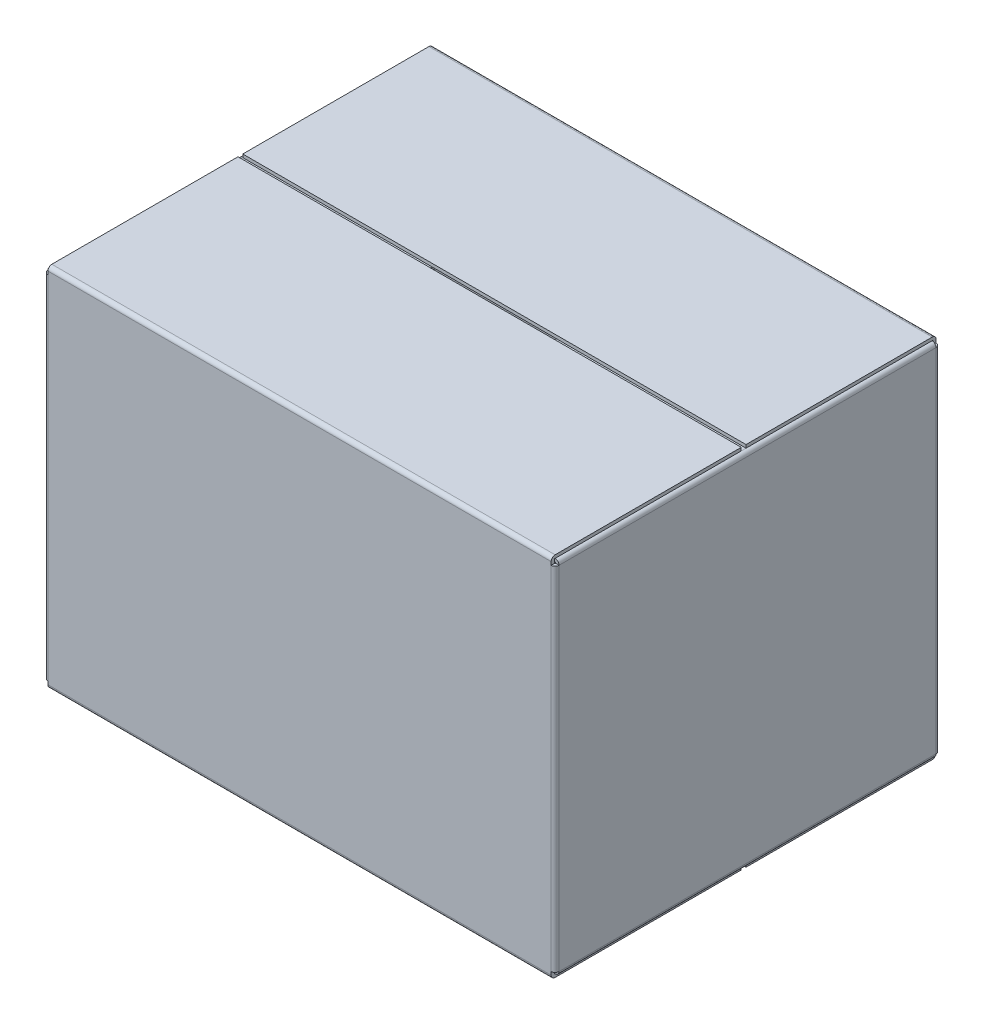
SolidWorks part; units mm, degrees
ref_plane "FRONT" through (0, 0, 0) normal (0, 0, 1) x (1, 0, 0)
ref_plane "TOP" through (0, 0, 0) normal (0, 1, 0) x (1, 0, 0)
ref_plane "RIGHT" through (0, 0, 0) normal (1, 0, 0) x (0, 0, -1)
ref_axis "X_Axis" through (-31.1439, 0, 0) along (1, 0, 0)
ref_axis "Y_Axis" through (0, 30.3761, 0) along (0, -1, 0)
ref_axis "Z_Axis" through (0, 0, -30.2246) along (0, 0, 1)
sketch "Sketch1" plane through (0, 0, 0) normal (0, 1, 0) x (1, 0, 0)
  line L0 (-253.2062, -190.5) -> (253.2062, -190.5)
  line L1 (-253.2062, 189.7062) -> (253.2062, -189.7062) construction
  line L2 (257.175, -189.7062) -> (257.175, 189.7062)
  line L3 (-254, -189.7062) -> (-254, 189.7062)
  line L4 (253.2062, 193.675) -> (-253.2062, 193.675)
  line L5 (254, -189.7062) -> (254, 189.7062)
  line L6 (253.2062, 190.5) -> (-253.2062, 190.5)
  line L7 (-257.175, -189.7062) -> (-257.175, 189.7062)
  line L8 (-253.2062, -193.675) -> (253.2062, -193.675)
  arc A0 (-253.2062, -190.5) -> (-254, -189.7062) centre (-253.2062, -189.7062) cw
  arc A1 (257.175, 189.7062) -> (253.2062, 193.675) centre (253.2062, 189.7062) ccw
  arc A2 (253.2062, -190.5) -> (254, -189.7062) centre (253.2062, -189.7062) ccw
  arc A3 (-257.175, 189.7062) -> (-253.2062, 193.675) centre (-253.2062, 189.7062) cw
  arc A4 (-254, 189.7062) -> (-253.2062, 190.5) centre (-253.2062, 189.7062) cw
  arc A5 (-253.2062, -193.675) -> (-257.175, -189.7062) centre (-253.2062, -189.7062) cw
  arc A6 (253.2062, -193.675) -> (257.175, -189.7062) centre (253.2062, -189.7062) ccw
  arc A7 (254, 189.7062) -> (253.2062, 190.5) centre (253.2062, 189.7062) ccw
  dimension "Inside_Radius" = 0.7937
  dimension "D2" = 514.35
  dimension "D1" = 387.35
  dimension "Wall_Thickness" = 3.175
extrude "Extrude1" add sketch "Sketch1" along normal mid plane 355.6
sketch "Sketch2" plane through (0, 177.8, 0) normal (0, 1, 0) x (1, 0, 0)
  line L4 (257.175, -189.7062) -> (257.175, 189.7062)
  line L5 (253.2062, 193.675) -> (-253.2062, 193.675)
  line L6 (-257.175, 189.7062) -> (-257.175, -189.7062)
  line L7 (-253.2062, -193.675) -> (253.2062, -193.675)
  line L8 (257.175, -189.7062) -> (257.175, 189.7062)
  line L9 (253.2062, 193.675) -> (-253.2062, 193.675)
  line L10 (-257.175, 189.7062) -> (-257.175, -189.7062)
  line L11 (-253.2062, -193.675) -> (253.2062, -193.675)
  arc A4 (253.2062, -193.675) -> (257.175, -189.7062) centre (253.2062, -189.7062) ccw
  arc A5 (257.175, 189.7062) -> (253.2062, 193.675) centre (253.2062, 189.7062) ccw
  arc A6 (-253.2062, 193.675) -> (-257.175, 189.7062) centre (-253.2062, 189.7062) ccw
  arc A7 (-257.175, -189.7062) -> (-253.2062, -193.675) centre (-253.2062, -189.7062) ccw
  arc A8 (253.2062, -193.675) -> (257.175, -189.7062) centre (253.2062, -189.7062) ccw
  arc A9 (257.175, 189.7062) -> (253.2062, 193.675) centre (253.2062, 189.7062) ccw
  arc A10 (-253.2062, 193.675) -> (-257.175, 189.7062) centre (-253.2062, 189.7062) ccw
  arc A11 (-257.175, -189.7062) -> (-253.2062, -193.675) centre (-253.2062, -189.7062) ccw
  dimension "D1" = 0
extrude "Cut-Extrude1" cut sketch "Sketch2" against normal blind 0.7937
sketch "Sketch3" plane through (0, -177.8, 0) normal (0, -1, 0) x (1, 0, 0)
  line L4 (253.2062, 193.675) -> (-253.2062, 193.675)
  line L5 (-257.175, 189.7062) -> (-257.175, -189.7062)
  line L6 (-253.2062, -193.675) -> (253.2062, -193.675)
  line L7 (257.175, -189.7062) -> (257.175, 189.7062)
  line L8 (253.2062, 193.675) -> (-253.2062, 193.675)
  line L9 (-257.175, 189.7062) -> (-257.175, -189.7062)
  line L10 (-253.2062, -193.675) -> (253.2062, -193.675)
  line L11 (257.175, -189.7062) -> (257.175, 189.7062)
  arc A4 (257.175, 189.7062) -> (253.2062, 193.675) centre (253.2062, 189.7062) ccw
  arc A5 (-253.2062, 193.675) -> (-257.175, 189.7062) centre (-253.2062, 189.7062) ccw
  arc A6 (-257.175, -189.7062) -> (-253.2062, -193.675) centre (-253.2062, -189.7062) ccw
  arc A7 (253.2062, -193.675) -> (257.175, -189.7062) centre (253.2062, -189.7062) ccw
  arc A8 (257.175, 189.7062) -> (253.2062, 193.675) centre (253.2062, 189.7062) ccw
  arc A9 (-253.2062, 193.675) -> (-257.175, 189.7062) centre (-253.2062, 189.7062) ccw
  arc A10 (-257.175, -189.7062) -> (-253.2062, -193.675) centre (-253.2062, -189.7062) ccw
  arc A11 (253.2062, -193.675) -> (257.175, -189.7062) centre (253.2062, -189.7062) ccw
  dimension "D1" = 0
extrude "Cut-Extrude2" cut sketch "Sketch3" against normal blind 0.7937
sketch "Sketch4" plane through (0, 0, 0) normal (0, 0, 1) x (1, 0, 0)
  line L0 (-257.175, 177.0062) -> (-254, 177.0062)
  line L1 (-253.2063, 180.975) -> (-62.7063, 180.975)
  line L2 (-253.2063, 177.8) -> (-62.7063, 177.8)
  line L3 (-62.7063, 177.8) -> (-62.7063, 180.975)
  line L4 (0, 0) -> (0, 180.975) construction
  line L5 (62.7063, 177.8) -> (62.7063, 180.975)
  line L6 (253.2063, 177.8) -> (62.7063, 177.8)
  line L7 (253.2063, 180.975) -> (62.7063, 180.975)
  line L8 (257.175, 177.0062) -> (254, 177.0062)
  line L9 (-257.175, 0) -> (257.175, 0) construction
  line L10 (-257.175, 177.0062) -> (-257.175, -177.0062) construction
  line L11 (257.175, -177.0062) -> (254, -177.0062)
  line L12 (253.2063, -180.975) -> (62.7063, -180.975)
  line L13 (253.2063, -177.8) -> (62.7063, -177.8)
  line L14 (62.7063, -177.8) -> (62.7063, -180.975)
  line L15 (-62.7063, -177.8) -> (-62.7063, -180.975)
  line L16 (-253.2063, -177.8) -> (-62.7063, -177.8)
  line L17 (-253.2063, -180.975) -> (-62.7063, -180.975)
  line L18 (-257.175, -177.0062) -> (-254, -177.0062)
  arc A0 (-257.175, 177.0062) -> (-253.2063, 180.975) centre (-253.2063, 177.0062) cw
  arc A1 (-254, 177.0062) -> (-253.2063, 177.8) centre (-253.2063, 177.0062) cw
  arc A2 (254, 177.0062) -> (253.2063, 177.8) centre (253.2063, 177.0062) ccw
  arc A3 (257.175, 177.0062) -> (253.2063, 180.975) centre (253.2063, 177.0062) ccw
  arc A4 (257.175, -177.0062) -> (253.2063, -180.975) centre (253.2063, -177.0062) cw
  arc A5 (254, -177.0062) -> (253.2063, -177.8) centre (253.2063, -177.0062) cw
  arc A6 (-254, -177.0062) -> (-253.2063, -177.8) centre (-253.2063, -177.0062) ccw
  arc A7 (-257.175, -177.0062) -> (-253.2063, -180.975) centre (-253.2063, -177.0062) ccw
  dimension "D2" = 0.7937
  dimension "D1" = 190.5
extrude "Extrude2" add sketch "Sketch4" along normal up to vertex (189.7063 mm away) and the other way up to vertex (189.7063 mm away) up to point (-254, 177.0062, 189.7062) other way up to point (-254, 177.0062, -189.7062)
sketch "Sketch5" plane through (0, 0, 0) normal (1, 0, 0) x (0, 0, -1)
  line L0 (-193.675, 177.0062) -> (-190.5, 177.0062)
  line L1 (-190.5, 177.0062) -> (-190.5, 180.2067)
  line L2 (-193.675, 177.0062) -> (-193.675, 180.2066)
  line L3 (-189.7063, 184.1754) -> (-2.4067, 184.1754)
  line L4 (-189.7063, 181.0004) -> (-2.4067, 181.0004)
  line L5 (-2.4067, 181.0004) -> (-2.4067, 184.1754)
  line L7 (0, 184.1754) -> (0, -184.1754) construction
  line L8 (-193.675, 0) -> (193.675, 0) construction
  line L9 (2.4067, 181.0004) -> (2.4067, 184.1754)
  line L10 (189.7063, 181.0004) -> (2.4067, 181.0004)
  line L11 (189.7063, 184.1754) -> (2.4067, 184.1754)
  line L12 (193.675, 177.0063) -> (193.675, 180.2067)
  line L13 (190.5, 177.0063) -> (190.5, 180.2067)
  line L14 (193.675, 177.0063) -> (190.5, 177.0063)
  line L15 (193.675, -177.0062) -> (190.5, -177.0062)
  line L16 (190.5, -177.0062) -> (190.5, -180.2067)
  line L17 (193.675, -177.0062) -> (193.675, -180.2066)
  line L18 (189.7063, -184.1754) -> (2.4067, -184.1754)
  line L19 (189.7063, -181.0004) -> (2.4067, -181.0004)
  line L20 (2.4067, -181.0004) -> (2.4067, -184.1754)
  line L21 (-2.4067, -181.0004) -> (-2.4067, -184.1754)
  line L22 (-189.7062, -181.0004) -> (-2.4067, -181.0004)
  line L23 (-189.7062, -184.1754) -> (-2.4067, -184.1754)
  line L24 (-193.675, -177.0063) -> (-193.675, -180.2067)
  line L25 (-190.5, -177.0063) -> (-190.5, -180.2067)
  line L26 (-193.675, -177.0063) -> (-190.5, -177.0063)
  arc A0 (-190.5, 180.2067) -> (-189.7063, 181.0004) centre (-189.7063, 180.2066) cw
  arc A1 (-193.675, 180.2066) -> (-189.7063, 184.1754) centre (-189.7063, 180.2066) cw
  arc A2 (193.675, 180.2067) -> (189.7063, 184.1754) centre (189.7063, 180.2067) ccw
  arc A3 (190.5, 180.2067) -> (189.7063, 181.0004) centre (189.7063, 180.2067) ccw
  arc A4 (190.5, -180.2067) -> (189.7063, -181.0004) centre (189.7063, -180.2066) cw
  arc A5 (193.675, -180.2066) -> (189.7063, -184.1754) centre (189.7063, -180.2066) cw
  arc A6 (-193.675, -180.2067) -> (-189.7062, -184.1754) centre (-189.7062, -180.2067) ccw
  arc A7 (-190.5, -180.2067) -> (-189.7062, -181.0004) centre (-189.7062, -180.2067) ccw
  dimension "D1" = 0.7937
  dimension "D3" = 3.2004
  dimension "D2" = 187.2996
extrude "Extrude3" add sketch "Sketch5" along normal up to vertex (253.2063 mm away) and the other way up to vertex (253.2063 mm away) up to point (253.2063, 177.0062, 190.5) other way up to point (-253.2063, 177.0062, 190.5)
sketch "Sketch6" plane through (0, -184.1754, 0) normal (0, -1, 0) x (1, 0, 0)
  line L0 (-253.2062, -34.1567) -> (253.2062, -34.1567) construction
  line L1 (-253.2062, -2.4067) -> (-253.2062, -189.7063) construction
  line L2 (253.2062, -2.4067) -> (253.2062, -189.7063) construction
  line L3 (253.2062, -2.4067) -> (-253.2062, -2.4067) construction
  text T0 "400001151" font "Arial Narrow" height 19.05
  dimension "D1" = 31.75
extrude "Cut-Extrude3" cut sketch "Sketch6" against normal blind 0.0025
sketch "Sketch7" plane through (257.175, 0, 0) normal (1, 0, 0) x (0, 0, -1)
  line L0 (-189.7062, -184.1754) -> (-2.4067, -184.1754) construction
  line L1 (-189.7062, -184.1754) -> (-2.4067, -184.1754)
  line L2 (-2.4067, 184.1754) -> (-189.7063, 184.1754) construction
  line L3 (-2.4067, 184.1754) -> (-189.7063, 184.1754)
  dimension "D1" = 368.3508
scale "Scale1" bodies to scale 133 scale about origin uniform scaling yes scale factor 0.5
scale "Scale2" scale about origin uniform scaling yes scale factor 0.9
scale "Scale3" scale about origin uniform scaling yes scale factor 0.5
scale "Scale4" scale about origin uniform scaling yes scale factor 0.5
scale "Scale5" scale about origin uniform scaling yes scale factor 0.2
scale "Scale6" scale about origin uniform scaling yes scale factor 3
scale "Scale7" scale about origin uniform scaling yes scale factor 0.75
equation "\"D1@Cut-Extrude1\" = \"Inside_Radius@Sketch1\""
equation "\"D1@Cut-Extrude2\"=\"Inside_Radius@Sketch1\""
equation "\"D2@Sketch4\" = \"Inside_Radius@Sketch1\""
equation "\"D1@Sketch4\"=  \"Width@Sketch1\" / 2 "
equation "\"D1@Sketch5\" = \"Inside_Radius@Sketch1\""
equation "\"D2@Sketch5\" = \"D1@Sketch4\"-\"D3@Sketch5\""
equation "\"D3@Sketch5\" = \"Wall_Thickness@Sketch1\"+.001"
